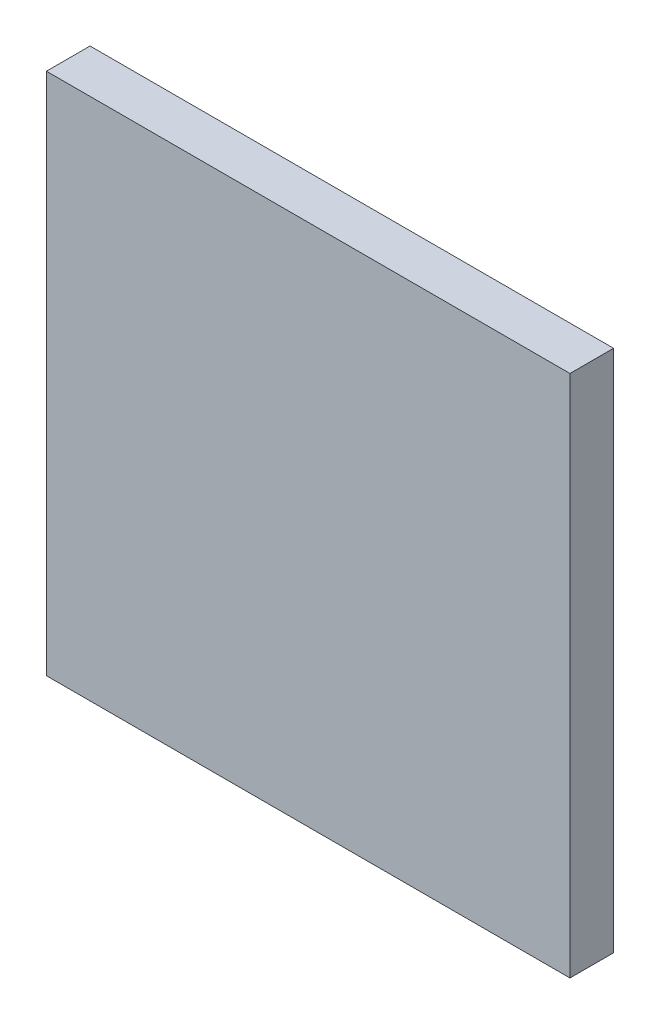
SolidWorks part; units mm, degrees
ref_plane "Front Plane" through (0, 0, 0) normal (0, 0, 1) x (1, 0, 0)
ref_plane "Top Plane" through (0, 0, 0) normal (0, 1, 0) x (1, 0, 0)
ref_plane "Right Plane" through (0, 0, 0) normal (1, 0, 0) x (0, 0, -1)
sketch "Sketch1" plane through (0, 0, 0) normal (0, 0, 1) x (1, 0, 0)
  line L1 (0, 0) -> (0.12, 0)
  line L2 (0, 0) -> (0, 0.12)
  line L3 (0, 0.12) -> (0.12, 0.12)
  line L4 (0.12, 0) -> (0.12, 0.12)
  dimension "D1" = 0.12
  dimension "D2" = 0.12
extrude "Boss-Extrude1" add sketch "Sketch1" along normal blind 0.01
